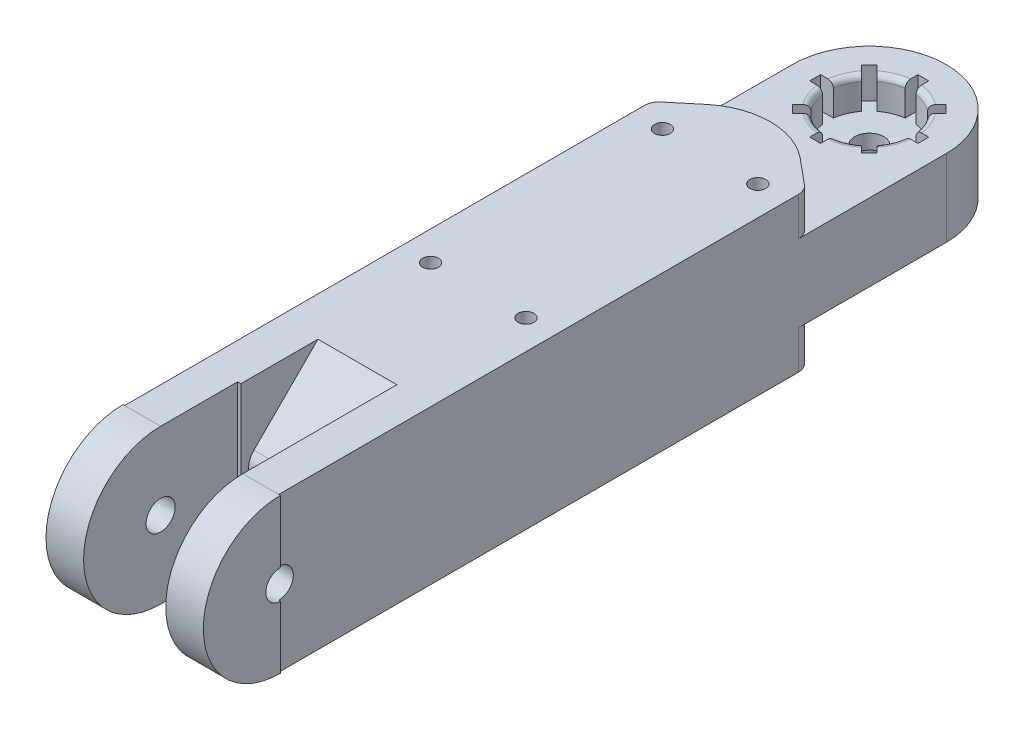
SolidWorks part; units mm, degrees
ref_plane "Front Plane" through (0, 0, 0) normal (0, 0, 1) x (1, 0, 0)
ref_plane "Top Plane" through (0, 0, 0) normal (0, 1, 0) x (1, 0, 0)
ref_plane "Right Plane" through (0, 0, 0) normal (1, 0, 0) x (0, 0, -1)
sketch "Sketch1" plane through (0, 0, 0) normal (0, 0, 1) x (1, 0, 0)
  line L1 (-21, 21) -> (21, 21)
  line L2 (-21, 21) -> (-21, -21)
  line L3 (-21, -21) -> (21, -21)
  line L4 (21, 21) -> (21, -21)
  line L5 (-21, 21) -> (21, -21) construction
  line L6 (-21, -21) -> (21, 21) construction
  point P0 (0, 0)
  dimension "D1" = 42
  dimension "D2" = 42
extrude "Boss-Extrude1" add sketch "Sketch1" along normal blind 140
ref_plane "Plane1" through (0, 0, 140) normal (0, 0, 1) x (1, 0, 0)
sketch "Sketch2" plane through (0, 0, 140) normal (0, 0, 1) x (1, 0, 0)
  line L0 (-21, -21) -> (21, -21) construction
  line L1 (-21, 21) -> (-11.2, 21)
  line L2 (-21, 21) -> (-21, -21)
  line L3 (-21, -21) -> (-11.2, -21)
  line L4 (-11.2, 21) -> (-11.2, -21)
  line L5 (21, 21) -> (-21, 21) construction
  line L6 (21, -21) -> (11.2, -21)
  line L7 (21, -21) -> (21, 21)
  line L8 (21, 21) -> (11.2, 21)
  line L9 (11.2, -21) -> (11.2, 21)
  dimension "D1" = 9.8
  dimension "D2" = 9.8
extrude "Boss-Extrude2" add sketch "Sketch2" along normal blind 21
ref_plane "Plane2" through (-11.2, 0, 0) normal (1, 0, 0) x (0, 0, -1)
sketch "Sketch3" plane through (-11.2, 0, 0) normal (1, 0, 0) x (0, 0, -1)
  line L0 (-161, -21) -> (-161, 21)
  arc A0 (-161, -21) -> (-161, 21) centre (-161, 0) cw
  dimension "D1" = 21
ref_plane "Plane3" through (0, -21, 0) normal (0, -1, 0) x (-1, 0, 0)
ref_plane "Plane4" through (11.2, 0, 0) normal (-1, 0, 0) x (0, 0, 1)
sketch "Sketch5" plane through (11.2, 0, 0) normal (-1, 0, 0) x (0, 0, 1)
  line L0 (161, 21) -> (161, -21)
  line L4 (140, 21) -> (140, -21)
  line L5 (140, -21) -> (161, -21)
  line L6 (161, -21) -> (161, 21)
  line L7 (161, 21) -> (140, 21)
  line L8 (140, 21) -> (140, -21)
  line L9 (140, -21) -> (161, -21)
  line L11 (161, 21) -> (140, 21)
  arc A0 (161, 21) -> (161, -21) centre (161, 0) cw
  dimension "D1" = 21
  dimension "D2" = 0
extrude "Boss-Extrude4" add sketch "Sketch5" against normal blind 10.25 contours A0 L0 region at (11.2, 0, 169.9127)
extrude "Boss-Extrude5" add sketch "Sketch3" against normal blind 10.25
sketch "Sketch6" plane through (11.2, 0, 0) normal (-1, 0, 0) x (0, 0, 1)
  line L0 (161, -21) -> (161, 21) construction
  circle A0 centre (161, 0) radius 3.975
  dimension "D1" = 7.95
extrude "Cut-Extrude1" cut sketch "Sketch6" against normal through all
ref_plane "Plane5" through (-11.2, 0, 0) normal (1, 0, 0) x (0, 0, -1)
sketch "Sketch8" plane through (-11.2, 0, 0) normal (1, 0, 0) x (0, 0, -1)
  line L0 (-161, -21) -> (-161, 21) construction
  circle A0 centre (-161, 0) radius 3.975
  dimension "D1" = 7.95
extrude "Cut-Extrude2" cut sketch "Sketch8" against normal through all
ref_plane "Plane6" through (0, 0, 0) normal (0, 0, -1) x (-1, 0, 0)
sketch "Sketch9" plane through (0, 0, 0) normal (0, 0, -1) x (-1, 0, 0)
  line L0 (21, 21) -> (21, -21) construction
  line L1 (21, 10.5) -> (-21, 10.5)
  line L2 (21, 10.5) -> (21, -10.5)
  line L3 (21, -10.5) -> (-21, -10.5)
  line L4 (-21, 10.5) -> (-21, -10.5)
  line L5 (-21, -21) -> (-21, 21) construction
  line L6 (-21, 21) -> (21, 21) construction
  line L7 (21, -21) -> (-21, -21) construction
  dimension "D1" = 10.5
  dimension "D2" = 10.5
extrude "Boss-Extrude6" add sketch "Sketch9" along normal blind 21
ref_plane "Plane7" through (0, -10.5, 0) normal (0, -1, 0) x (-1, 0, 0)
sketch "Sketch10" plane through (0, -10.5, 0) normal (0, -1, 0) x (-1, 0, 0)
  line L0 (-21, 21) -> (21, 21)
  arc A0 (-21, 21) -> (21, 21) centre (0, 21) cw
  dimension "D1" = 21
extrude "Boss-Extrude7" add sketch "Sketch10" against normal blind 21
sketch "Sketch11" plane through (0, -10.5, 0) normal (0, -1, 0) x (-1, 0, 0)
  line L0 (21, 21) -> (-21, 21) construction
  circle A0 centre (0, 21) radius 11.35
  dimension "D1" = 22.7
extrude "Cut-Extrude3" cut sketch "Sketch11" against normal blind 8.5
ref_plane "Plane8" through (11.2, 0, 0) normal (-1, 0, 0) x (0, 0, 1)
sketch "Sketch16" plane through (11.2, 0, 0) normal (-1, 0, 0) x (0, 0, 1)
  line L0 (140, 21) -> (140, 0)
  line L1 (140, 21) -> (140, -21) construction
  line L2 (140, 0) -> (140, -21)
  line L3 (140, -21) -> (119, -21)
  line L4 (119, -21) -> (140, 0)
  line L5 (140, 21) -> (119, 21)
  line L6 (119, 21) -> (140, 0)
  line L7 (161, 0) -> (140, 0) construction
  dimension "D1" = 21
  dimension "D2" = 21
extrude "Cut-Extrude4" cut sketch "Sketch16" along normal blind 21.5 contours L0 L5 L6 | L2 L3 L4
fillet "Fillet1" radius 5 1 edges at (0.45, 0, 140)
ref_plane "Plane9" through (0, -10.5, 0) normal (0, -1, 0) x (-1, 0, 0)
ref_plane "Plane10" through (0, 10.5, 0) normal (0, 1, 0) x (1, 0, 0)
sketch "Sketch18" plane through (0, 10.5, 0) normal (0, 1, 0) x (1, 0, 0)
  line L0 (21, 21) -> (-21, 21) construction
  circle A0 centre (0, 21) radius 11.35
  dimension "D1" = 22.7
extrude "Cut-Extrude5" cut sketch "Sketch18" against normal blind 8.5
sketch "Sketch19" plane through (0, -2, 0) normal (0, -1, 0) x (1, 0, 0)
  circle A0 centre (0, -21) radius 3.975
  dimension "D1" = 7.95
extrude "Cut-Extrude6" cut sketch "Sketch19" against normal blind 8.5
fillet "Fillet4" radius 1.5 1 edges at (11.35, -10.5, -21)
fillet "Fillet5" radius 1.5 1 edges at (-11.35, 10.5, -21)
sketch "Sketch20" plane through (0, 10.5, 0) normal (0, 1, 0) x (1, 0, 0)
  line L1 (-1.48, 35.755) -> (1.48, 35.755)
  line L2 (-1.48, 35.755) -> (-1.48, 31.945)
  line L3 (-1.48, 31.945) -> (1.48, 31.945)
  line L4 (1.48, 35.755) -> (1.48, 31.945)
  line L5 (-1.48, 35.755) -> (1.48, 31.945) construction
  line L6 (-1.48, 31.945) -> (1.48, 35.755) construction
  circle A0 centre (0, 21) radius 12.85 construction
  point P0 (0, 33.85)
  dimension "D1" = 2.96
  dimension "D2" = 3.81
extrude "Cut-Extrude7" cut sketch "Sketch20" against normal blind 8.5
pattern_circular "CirPattern1" count 8 over 360 about axis through (0, 2, -21) along (0, 1, 0) of "Cut-Extrude7"
ref_plane "Plane11" through (0, 0, 0) normal (0, 1, 0) x (1, 0, 0)
mirror "Mirror1" about plane through (0, 0, 0) normal (0, 1, 0) of "CirPattern1"
sketch "Sketch25" plane through (0, -21, 0) normal (0, -1, 0) x (1, 0, 0)
  line L0 (0, 0) -> (0, 119) construction
  line L2 (-21, 0) -> (21, 0) construction
  line L3 (17, 78.5) -> (-17, 78.5)
  line L4 (17, 78.5) -> (17, 29.5)
  line L5 (17, 29.5) -> (-17, 29.5)
  line L6 (-17, 78.5) -> (-17, 29.5)
  line L7 (17, 78.5) -> (-17, 29.5) construction
  line L8 (17, 29.5) -> (-17, 78.5) construction
  point P5 (0, 54)
  dimension "D1" = 34
  dimension "D2" = 49
  dimension "D3" = 54
extrude "Cut-Extrude11" cut sketch "Sketch25" against normal blind 32 contours L3 L6 L5 L4 region at (0, -21, 54)
sketch "Sketch26" plane through (0, -21, 0) normal (0, -1, 0) x (1, 0, 0)
  line L0 (0, 29.5) -> (0, 18.4) construction
  line L1 (17, 29.5) -> (-17, 29.5)
  line L2 (17, 29.5) -> (17, 26.5)
  line L3 (17, 26.5) -> (-17, 26.5)
  line L4 (-17, 29.5) -> (-17, 26.5)
  line L5 (-17, 26.5) -> (17, 26.5)
  line L6 (-17, 26.5) -> (-17, 18.4)
  line L7 (-17, 18.4) -> (17, 18.4)
  line L8 (17, 26.5) -> (17, 18.4)
  line M6 (17, 29.5) -> (-17, 29.5)
  line M7 (-21, 0) -> (21, 0)
  dimension "D1" = 3
  dimension "D2" = 8.1
extrude "Cut-Extrude12" cut sketch "Sketch26" against normal blind 27 contours L3 L0 L8 M7 | L0 L3 L2 M6 | L0 L1 L4 L5 | L0 L5 L6 M7 | L0 L6 L7 M7 | L0 L7 L8 M7 region at (8.5, -21, 28) region at (-8.5, -21, 28) region at (8.5, -21, 22.45) region at (-8.5, -21, 22.45)
sketch "Sketch30" plane through (0, 6, 0) normal (0, -1, 0) x (1, 0, 0)
  line L0 (0, 29.5) -> (0, 18.4) construction
  line L1 (17, 29.5) -> (-17, 29.5) construction
  line L2 (-17, 18.4) -> (17, 18.4) construction
  line L3 (-17, 29.5) -> (-17, 18.4) construction
  circle A0 centre (-13, 22.4) radius 4
  circle A1 centre (-13, 22.4) radius 2.15
  dimension "D1" = 8
  dimension "D2" = 4.3
extrude "Cut-Extrude13" cut sketch "Sketch30" against normal through all contours A1 region at (-13, 6, 22.4)
ref_plane "Plane12" through (0, 0, 0) normal (-1, 0, 0) x (0, 0, 1)
mirror "Mirror9" about plane through (0, 0, 0) normal (-1, 0, 0) of "Cut-Extrude13"
ref_plane "Plane13" through (0, 0, 54) normal (0, 0, 1) x (1, 0, 0)
sketch "Sketch32" plane through (0, 21, 0) normal (0, 1, 0) x (1, 0, 0)
  line L3 (0, 0) -> (0, -65.7087) construction
  line L4 (0, 17.6) -> (0, -17.6) construction
  line L10 (0, 0) -> (21, -17.4215)
  line L11 (21, -161) -> (21, 0) construction
  line L13 (-21, -161) -> (-21, 0) construction
  line L14 (-21, -17.4215) -> (0, 0)
  line L15 (0, 0) -> (-21, 0)
  line L16 (-21, 0) -> (-21, -17.4215)
  line L17 (0, 0) -> (21, 0)
  line L18 (21, 0) -> (21, -17.4215)
  line M13 (21, -161) -> (21, 0)
  line M14 (21, 0) -> (-21, 0)
  line M15 (-21, 0) -> (-21, -161)
fillet "Fillet10" radius 3 2 edges at (-17, -7.5, 18.4) (17, -7.5, 18.4)
ref_plane "Plane14" through (0, 0, 54) normal (0, 0, -1) x (-1, 0, 0)
mirror "Mirror12" about plane through (0, 0, 54) normal (0, 0, -1) of "Fillet10", "Mirror9", "Cut-Extrude13", "Cut-Extrude12"
extrude "Cut-Extrude16" cut sketch "Sketch32" against normal blind 10.5 contours L14 M15 M14 | L10 M14 M13 region at (14, 21, 5.8072) region at (-14, 21, 5.8072)
fillet "Fillet12" radius 20 1 edges at (0, 15.75, 0)
mirror "Mirror13" about plane through (0, 0, 0) normal (0, 1, 0) of "Fillet12", "Cut-Extrude16"
fillet "Fillet13" radius 4 4 edges at (-21, 15.75, 17.4215) (-21, -15.75, 17.4215) (21, -15.75, 17.4215) (21, 15.75, 17.4215)
